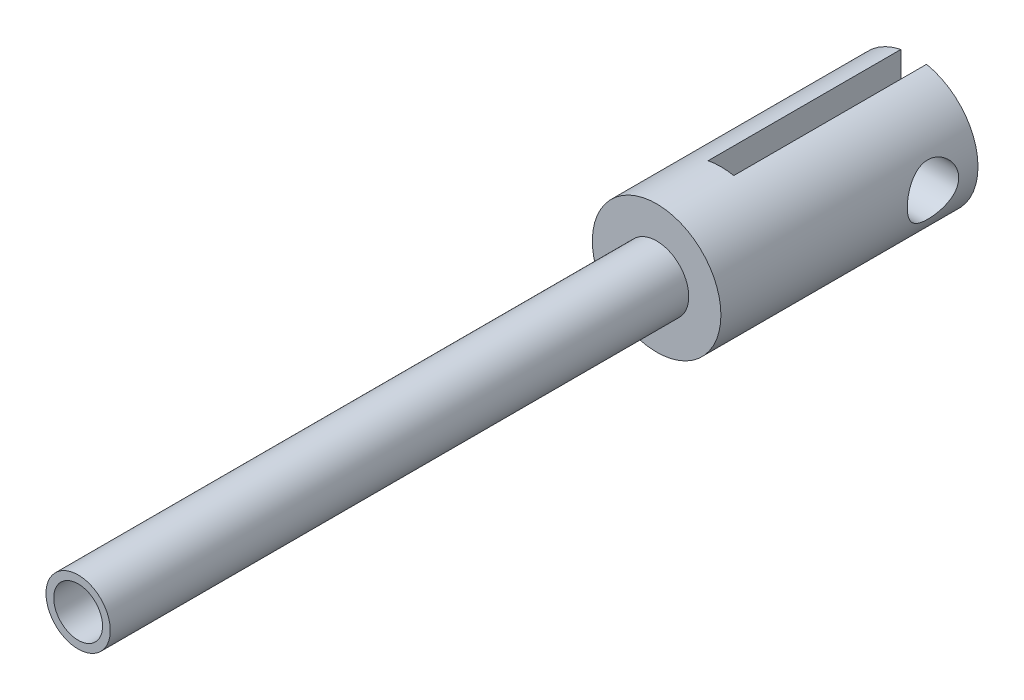
SolidWorks part; units mm, degrees
ref_plane "Front Plane" through (0, 0, 0) normal (0, 0, 1) x (1, 0, 0)
ref_plane "Top Plane" through (0, 0, 0) normal (0, 1, 0) x (1, 0, 0)
ref_plane "Right Plane" through (0, 0, 0) normal (1, 0, 0) x (0, 0, -1)
sketch "Sketch2" plane through (0, 0, 0) normal (0, 0, 1) x (1, 0, 0)
  circle A0 centre (0, 0) radius 10
extrude "Boss-Extrude1" add sketch "Sketch2" along normal blind 40
sketch "Sketch3" plane through (0, 0, 0) normal (0, 1, 0) x (1, 0, 0)
  line L1 (-2, 0) -> (2, 0)
  line L2 (10, 0) -> (-10, 0) construction
  line L3 (-2, 0) -> (-2, -30)
  line L4 (-2, -30) -> (2, -30)
  line L5 (2, -30) -> (2, 0)
  point P8 (0, 0)
extrude "Cut-Extrude1" cut sketch "Sketch3" against normal blind 20 and the other way blind 20
sketch "Sketch4" plane through (0, 0, 0) normal (1, 0, 0) x (0, 0, -1)
  circle A0 centre (-7, 0) radius 4
extrude "Cut-Extrude2" cut sketch "Sketch4" against normal blind 20 and the other way blind 20
sketch "Sketch5" plane through (0, 0, 40) normal (0, 0, 1) x (1, 0, 0)
  circle A1 centre (0, 0) radius 5
extrude "Boss-Extrude2" add sketch "Sketch5" along normal blind 90
sketch "Sketch6" plane through (0, 0, 130) normal (0, 0, 1) x (1, 0, 0)
  circle A0 centre (0, 0) radius 3.8
extrude "Cut-Extrude3" cut sketch "Sketch6" against normal blind 20
